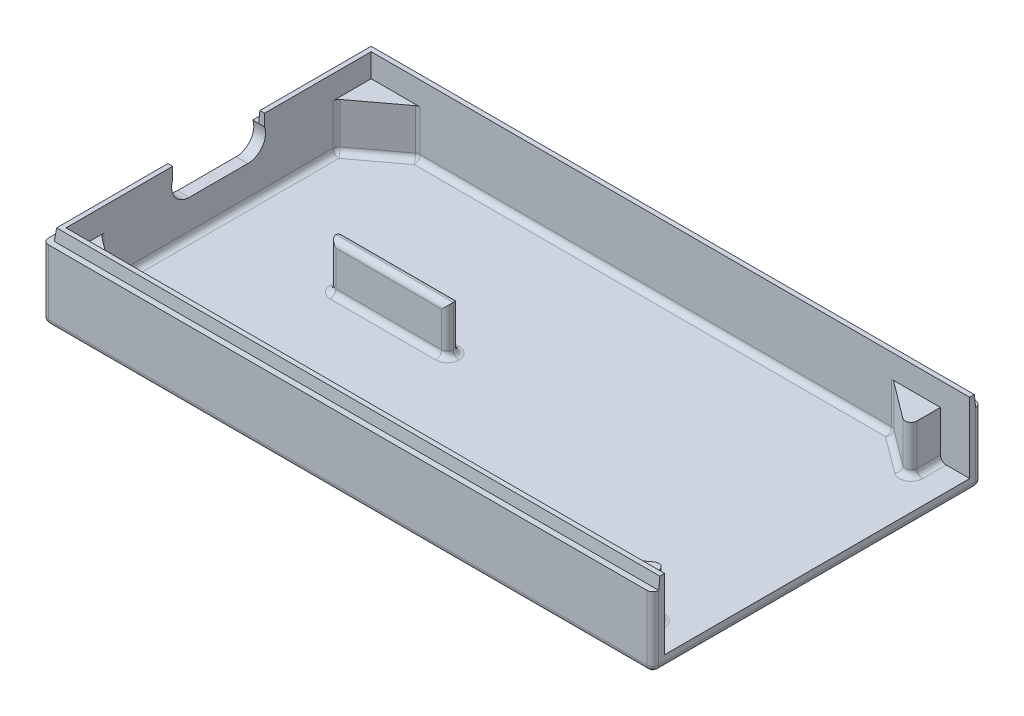
SolidWorks part; units mm, degrees
ref_plane "Спереди" through (0, 0, 0) normal (0, 0, 1) x (1, 0, 0)
ref_plane "Сверху" through (0, 0, 0) normal (0, 1, 0) x (1, 0, 0)
ref_plane "Справа" through (0, 0, 0) normal (1, 0, 0) x (0, 0, -1)
sketch "Эскиз1" plane through (0, 0, 0) normal (0, 1, 0) x (1, 0, 0)
  line L1 (-26, 14) -> (26, 14)
  line L2 (-26, 14) -> (-26, -14)
  line L3 (-26, -14) -> (26, -14)
  line L4 (26, 14) -> (26, -14)
  line L5 (-26, 14) -> (26, -14) construction
  line L6 (-26, -14) -> (26, 14) construction
  point P0 (0, 0)
  dimension "D1" = 28
  dimension "D2" = 52
extrude "Бобышка-Вытянуть1" add sketch "Эскиз1" along normal blind 6
sketch "Эскиз3" plane through (0, 6, 0) normal (0, 1, 0) x (1, 0, 0)
  line L0 (0, 0) -> (-35.16, 0) construction
  line L2 (-25, 13) -> (26, 13)
  line L3 (-25, 13) -> (-25, -13)
  line L4 (-25, -13) -> (26, -13)
  line L5 (26, 13) -> (26, -13)
  line L6 (-25, 13) -> (26, -13) construction
  line L7 (-25, -13) -> (26, 13) construction
  line L8 (26, -14) -> (26, 14) construction
  point P3 (0.5, 0)
  dimension "D1" = 51
  dimension "D2" = 26
extrude "Вырез-Вытянуть1" cut sketch "Эскиз3" against normal blind 5
sketch "Эскиз4" plane through (0, 1, 0) normal (0, 1, 0) x (1, 0, 0)
  line L0 (19.5, 13) -> (23.5, 10)
  line L1 (26, 13) -> (-25, 13) construction
  line L2 (23.5, 10) -> (23.5, 13)
  line L3 (23.5, 13) -> (19.5, 13)
  line L4 (-25, 13) -> (-25, -13) construction
  line L5 (0, 0) -> (39.6554, 0) construction
  line L6 (-25, 13) -> (-25, 10)
  line L7 (-25, 13) -> (-25, -13) construction
  line L8 (-25, 10) -> (-21, 13)
  line L9 (-21, 13) -> (-25, 13)
  line L10 (-21, -13) -> (-25, -13)
  line L11 (-25, -10) -> (-21, -13)
  line L12 (-25, -13) -> (-25, -10)
  line L13 (23.5, -13) -> (19.5, -13)
  line L14 (23.5, -10) -> (23.5, -13)
  line L15 (19.5, -13) -> (23.5, -10)
  line L17 (-15, 0.5) -> (-5, 0.5)
  line L18 (-15, 0.5) -> (-15, -0.5)
  line L19 (-15, -0.5) -> (-5, -0.5)
  line L20 (-5, 0.5) -> (-5, -0.5)
  line L21 (-15, 0.5) -> (-5, -0.5) construction
  line L22 (-15, -0.5) -> (-5, 0.5) construction
  point P22 (-10, 0)
  dimension "D1" = 3
  dimension "D2" = 4
  dimension "D3" = 48.5
  dimension "D4" = 10
  dimension "D5" = 10
  dimension "D6" = 1
extrude "Бобышка-Вытянуть2" add sketch "Эскиз4" along normal blind 4
sketch "Эскиз5" plane through (-26, 0, 0) normal (-1, 0, 0) x (0, 0, 1)
  line L0 (0, 0) -> (0, 10.0488) construction
  line L1 (-14, 0) -> (14, 0) construction
  line L2 (2.5, 5.5) -> (-2.5, 5.5) construction
  line L3 (2.5, 4) -> (-2.5, 4)
  line L4 (2.5, 7) -> (-2.5, 7)
  line L5 (-14, 6) -> (14, 6) construction
  line L6 (-4, 8.575) -> (-4, 2.8797) construction
  line L7 (4, 8.575) -> (4, 2.4103) construction
  arc A0 (2.5, 4) -> (2.5, 7) centre (2.5, 5.5) ccw
  arc A1 (-2.5, 7) -> (-2.5, 4) centre (-2.5, 5.5) ccw
  point P6 (0, 5.5)
  dimension "D3" = 8
  dimension "D1" = 3
  dimension "D2" = 2
extrude "Вырез-Вытянуть2" cut sketch "Эскиз5" against normal up to next
fillet "Скругление1" radius 0.5 33 edges at (23.5, 1, -11.5) (23.5, 1, 11.5) (-5, 3, -0.5) (-10, 5, -0.5) (-15, 3, -0.5) (-10, 1, -0.5) (-15, 3, 0.5) (-10, 5, 0.5) (-5, 3, 0.5) (-10, 1, 0.5) (-21, 3, 13) (-23, 1, 11.5) (-25, 1, 0) (-25, 3, 10) (23.5, 3, -10) (19.5, 3, -13) (21.5, 1, -11.5) (23.5, 3, 10) (19.5, 3, 13) (21.5, 1, 11.5) (-0.75, 1, 13) (-0.75, 1, -13) (-25, 3, -10) (-23, 1, -11.5) (-21, 3, -13) (-26, 3, 14) (26, 3, 14) (26, 3, -14) (26, 0, 0) (0, 0, 14) (-26, 0, 0) (-26, 3, -14) (0, 0, -14)
sketch "Эскиз6" plane through (0, 6, 0) normal (0, 1, 0) x (1, 0, 0)
  line L0 (-25.5, 3.9142) -> (-25, 3.9142)
  line L1 (-26, 3.9142) -> (-25, 3.9142) construction
  line L2 (-25, 3.9142) -> (-25, 13)
  line L3 (-25, 13) -> (26, 13)
  line L4 (26, 13) -> (26, 13.5)
  line L5 (26, 13.5) -> (-25.5, 13.5)
  line L6 (-25.5, 13.5) -> (-25.5, 3.9142)
  line L7 (0, 0) -> (39.1176, 0) construction
  line L8 (-25.5, -13.5) -> (-25.5, -3.9142)
  line L9 (26, -13.5) -> (-25.5, -13.5)
  line L10 (26, -13) -> (26, -13.5)
  line L11 (-25, -13) -> (26, -13)
  line L12 (-25, -3.9142) -> (-25, -13)
  line L13 (-25.5, -3.9142) -> (-25, -3.9142)
  dimension "D1" = 0.5
extrude "Бобышка-Вытянуть3" add sketch "Эскиз6" along normal blind 1
chamfer "Фаска1" distance 1 distance2 0.1 4 edges at (0.25, 7, 13.5) (-25.5, 7, 8.7071) (0.25, 7, -13.5) (-25.5, 7, -8.7071)
